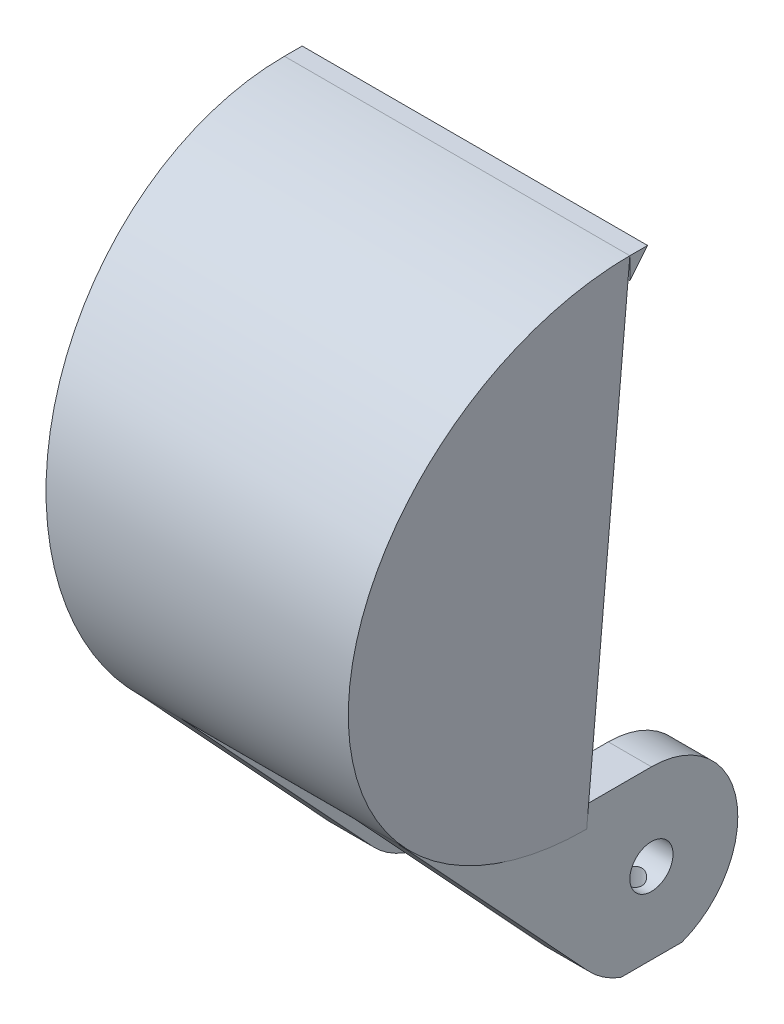
SolidWorks part; units mm, degrees
material "6061-T6 (SS)"
ref_plane "Front Plane" through (0, 0, 0) normal (0, 0, 1) x (1, 0, 0)
ref_plane "Top Plane" through (0, 0, 0) normal (0, 1, 0) x (1, 0, 0)
ref_plane "Right Plane" through (0, 0, 0) normal (1, 0, 0) x (0, 0, -1)
sketch "ExcavatorReferenceSize" plane through (0, 0, 0) normal (0, 1, 0) x (1, 0, 0)
  line L1 (-25.4, -12.7) -> (25.4, -12.7)
  line L2 (-25.4, -12.7) -> (-25.4, 12.7)
  line L3 (-25.4, 12.7) -> (25.4, 12.7)
  line L4 (25.4, -12.7) -> (25.4, 12.7)
  line L5 (-25.4, -12.7) -> (25.4, 12.7) construction
  line L6 (-25.4, 12.7) -> (25.4, -12.7) construction
  point P0 (0, 0)
  dimension "D1" = 25.4
  dimension "D2" = 50.8
sketch "Sketch2" plane through (0, 0, 0) normal (1, 0, 0) x (0, 0, -1)
  line L0 (0, 0) -> (0, 76.2)
  line L1 (0, 0) -> (8.9803, -8.9803) construction
  line L2 (0, 0) -> (0, 97.7406) construction
  arc A0 (0, 76.2) -> (0, 0) centre (0, 38.1) ccw
  dimension "D1" = 76.2
  dimension "D2" = 12.7
  dimension "D3" = 135
extrude "Boss-Extrude1" add sketch "Sketch2" along normal mid plane 50.8
sketch "Sketch15" plane through (0, 0, 0) normal (0, 0, -1) x (-1, 0, 0)
  line L0 (25.4, 76.2) -> (19.05, 0)
  line L1 (-25.4, 0) -> (25.4, 0) construction
  line L2 (0, 0) -> (0, 31.962) construction
  line L3 (25.4, 0) -> (19.05, 0)
  line L4 (25.4, 0) -> (25.4, 76.2)
  line L5 (-25.4, 0) -> (-19.05, 0)
  line L6 (-25.4, 76.2) -> (-19.05, 0)
  line L7 (-25.4, 0) -> (-25.4, 76.2)
  dimension "D1" = 6.35
extrude "Cut-Extrude9" cut sketch "Sketch15" against normal through all
shell "Shell1" thickness 3.175 removed face at (0, 38.1, 0)
chamfer "Chamfer1" [suppressed] distance 10 angle 45
sketch "Sketch4" plane through (0, 0, 0) normal (1, 0, 0) x (0, 0, -1)
  line L0 (0, 0) -> (31.6155, -31.6155) construction
  line L1 (0, 0) -> (0, 113.2937) construction
  circle A1 centre (9.525, -9.525) radius 12.7
  arc A2 (0, 73.025) -> (0, 3.175) centre (0, 38.1) ccw
  arc A3 (0, 73.025) -> (0, 3.175) centre (0, 38.1) ccw construction
  point P9 (9.525, 3.175)
  dimension "D1" = 25.4
  dimension "D2" = 135
  dimension "D3" = 12.7
extrude "Boss-Extrude3" add sketch "Sketch4" along normal mid plane 38.1
sketch "Sketch5" plane through (0, 0, 0) normal (1, 0, 0) x (0, 0, -1)
  line L4 (0, 3.175) -> (9.525, 3.175)
  line L5 (0, 0) -> (1.1247, 0)
  line L6 (0, 0) -> (0, 3.175)
  circle A0 centre (9.525, -9.525) radius 12.7 construction
  arc A1 (9.525, 3.175) -> (1.1247, 0) centre (9.525, -9.525) ccw
  dimension "D1" = 3.175
extrude "Boss-Extrude4" add sketch "Sketch5" along normal mid plane 38.1
sketch "Sketch6" plane through (0, 0, 0) normal (1, 0, 0) x (0, 0, -1)
  line L0 (0, 0) -> (12.9142, -12.9142) construction
  line L1 (0, 0) -> (0, 78.8833) construction
  circle A0 centre (9.525, -9.525) radius 12.7 construction
  circle A2 centre (9.525, -9.525) radius 12.7
  dimension "D1" = 225
extrude "Cut-Extrude2" cut sketch "Sketch6" against normal blind 12.7
extrude "Cut-Extrude3" cut sketch "Sketch6<2>" along normal blind 12.7
sketch "Sketch6<2>" plane through (0, 0, 0) normal (1, 0, 0) x (0, 0, -1) same geometry as "Sketch6"
sketch "Sketch7" plane through (-19.05, 0, 0) normal (-1, 0, 0) x (0, 0, 1)
  circle A2 centre (-9.525, -9.525) radius 12.7 construction
  circle A3 centre (-9.525, -9.525) radius 3.175
  circle A4 centre (-9.525, -9.525) radius 12.7 construction
  dimension "D1" = 6.35
extrude "Cut-Extrude4" cut sketch "Sketch7" against normal up to surface (38.1 mm away) up to face at (19.05, -4.1606, -4.835)
sketch "Sketch8" plane through (19.05, 0, 0) normal (1, 0, 0) x (0, 0, -1)
  line L3 (-27.9361, 12.1928) -> (0.213, -18.1607)
  line L6 (0.213, -18.1607) -> (5.0349, -21.4048)
  line L7 (-27.9361, 12.1928) -> (-25.2112, 13.9308)
  line L8 (5.0349, -21.4048) -> (1.1247, 0)
  line L9 (1.1247, 0) -> (-1.9187, 3.2277)
  line L10 (0, 0) -> (4.7601, 0) construction
  arc A0 (0, 76.2) -> (0, 0) centre (0, 38.1) ccw construction
  arc A2 (0, 76.2) -> (0, 0) centre (0, 38.1) ccw construction
  circle A3 centre (9.525, -9.525) radius 12.7 construction
  arc A6 (-27.9361, 12.1928) -> (0, 0) centre (0, 38.1) ccw construction
  arc A7 (22.225, -9.525) -> (0.213, -18.1607) centre (9.525, -9.525) ccw construction
  arc A9 (0, 73.025) -> (-34.9248, 38.2321) centre (0, 38.1) ccw
  arc A10 (-25.2112, 13.9308) -> (-1.9187, 3.2277) centre (0, 38.1) ccw
  circle A11 centre (9.525, -9.525) radius 12.7 construction
  point P10 (1.1247, 0)
  point P11 (-27.9361, 12.1928)
  point P12 (0.213, -18.1607)
  point P18 (-25.2112, 13.9308)
extrude "Boss-Extrude5" add sketch "Sketch8" against normal up to surface (38.1 mm away) up to face at (-19.05, -9.525, -6.35)
ref_plane "Plane1" through (0, -21.4048, 0) normal (0, 1, 0) x (1, 0, 0)
sketch "Sketch9" plane through (0, 0, 0) normal (1, 0, 0) x (0, 0, -1)
  line L3 (9.525, 3.175) -> (0, 3.175)
  line L5 (0, 3.175) -> (0, 0)
  line L13 (0, 3.175) -> (0, 0)
  line L15 (-27.9361, 12.1928) -> (0.213, -18.1607)
  line L16 (-27.9361, 12.1928) -> (0.213, -18.1607)
  line L17 (9.525, 3.175) -> (0, 3.175)
  arc A2 (-27.9361, 12.1928) -> (0, 0) centre (0, 38.1) ccw
  arc A3 (0.213, -18.1607) -> (9.525, 3.175) centre (9.525, -9.525) ccw
  arc A9 (-27.9361, 12.1928) -> (0, 0) centre (0, 38.1) ccw
  arc A10 (0.213, -18.1607) -> (9.525, 3.175) centre (9.525, -9.525) ccw
  dimension "D1" = 0
extrude "Cut-Extrude5" cut sketch "Sketch9" against normal mid plane 25.4
sketch "Sketch11" plane through (0, 0, 0) normal (1, 0, 0) x (0, 0, -1)
  line L0 (0, 76.2) -> (0, 73.025)
  line L8 (9.525, -9.525) -> (1.3049, 74.6125) construction
  line L9 (0, 76.2) -> (2.6098, 76.2)
  line L10 (2.6098, 76.2) -> (0, 73.025)
  arc A0 (0, 76.2) -> (0, 0) centre (0, 38.1) ccw construction
  circle A2 centre (9.525, -9.525) radius 3.175 construction
  arc A5 (0, 76.2) -> (0, 0) centre (0, 38.1) ccw construction
  circle A6 centre (9.525, -9.525) radius 3.175 construction
  arc A7 (0, 76.2) -> (0, 0) centre (0, 38.1) ccw construction
  dimension "D1" = 45
  dimension "D2" = 3.175
  dimension "D3" = 2.6098
extrude "Boss-Extrude6" add sketch "Sketch11" along normal mid plane 50.8 contours L10 L0 L9
ref_plane "Plane2" through (0, 73.025, 0) normal (0, -1, 0) x (-1, 0, 0)
fillet "Fillet2" radius 12.7 2 edges at (19.039, 38.1, 34.925) (-19.039, 38.1, 34.925)
sketch "Sketch12" plane through (0, -21.4048, 0) normal (0, 1, 0) x (1, 0, 0)
  line L1 (15.875, 12.7) -> (15.875, 6.35) construction
  line L2 (19.05, 0.213) -> (19.05, 22.225) construction
  line L3 (12.7, 22.225) -> (12.7, 0.213) construction
  line L4 (19.05, 0.213) -> (19.05, 22.225) construction
  line L5 (12.7, 22.225) -> (12.7, 0.213) construction
  line L6 (19.05, 11.219) -> (12.7, 11.219) construction
  line L7 (0, 0) -> (0, 34.6266) construction
  circle A0 centre (15.875, 9.525) radius 1.7526
  circle A1 centre (-15.875, 9.525) radius 1.7526
  point P4 (15.875, 9.525)
  point P13 (15.875, 11.219)
  dimension "D1" = 3.5052
extrude "Cut-Extrude6" cut sketch "Sketch12" along normal up to surface and the other way up to surface up to face at (19.05, -9.525, -12.7) other way up to face at (-15.875, -11.049, -13.0168)
sketch "Sketch13" plane through (0, -21.4048, 0) normal (0, 1, 0) x (1, 0, 0)
  line L0 (19.05, 15.875) -> (12.7, 15.875)
  line L2 (19.05, 15.875) -> (19.05, 3.175)
  line L3 (19.05, 3.175) -> (12.7, 3.175)
  line L4 (12.7, 10.3977) -> (12.7, 3.175)
  line L5 (12.7, 15.875) -> (12.7, 10.3977)
  line L6 (0, 0) -> (0, 23.3259) construction
  line L7 (-19.05, 15.875) -> (-12.7, 15.875)
  line L8 (-19.05, 15.875) -> (-19.05, 3.175)
  line L9 (-19.05, 3.175) -> (-12.7, 3.175)
  line L10 (-12.7, 10.3977) -> (-12.7, 3.175)
  line L11 (-12.7, 15.875) -> (-12.7, 10.3977)
  circle A0 centre (15.875, 9.525) radius 1.7526 construction
  circle A1 centre (15.875, 9.525) radius 1.7526 construction
  point P7 (15.875, 3.175)
  point P9 (19.05, 9.525)
  dimension "D1" = 12.7
  dimension "D2" = 6.35
extrude "Cut-Extrude7" cut sketch "Sketch13" against normal through all
